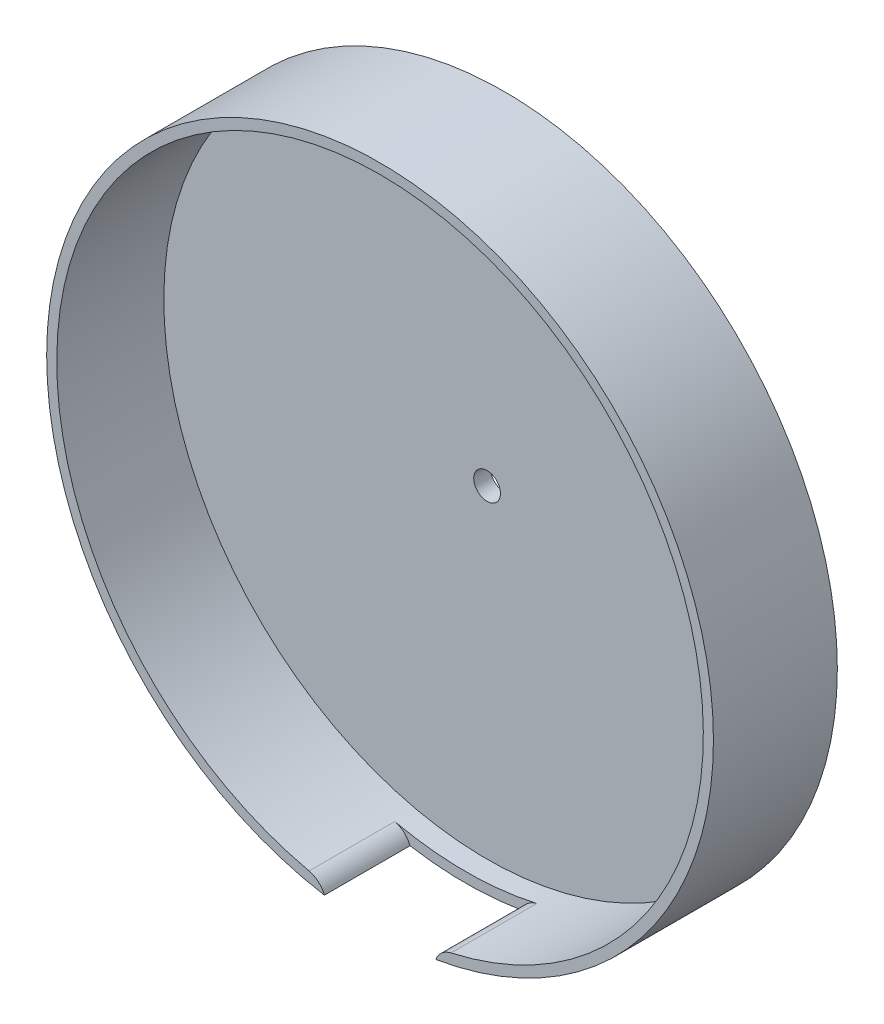
SolidWorks part; units mm, degrees
ref_plane "Front Plane" through (0, 0, 0) normal (0, 0, 1) x (1, 0, 0)
ref_plane "Top Plane" through (0, 0, 0) normal (0, 1, 0) x (1, 0, 0)
ref_plane "Right Plane" through (0, 0, 0) normal (1, 0, 0) x (0, 0, -1)
sketch "Sketch1" plane through (0, 0, 0) normal (0, 0, 1) x (1, 0, 0)
  circle A0 centre (0, 0) radius 38.1
  circle A1 centre (0, 0) radius 35.941
  dimension "D1" = 71.882
  dimension "D2" = 76.2
sketch "Sketch2" plane through (0, 0, 0) normal (0, 0, 1) x (1, 0, 0)
  circle A0 centre (0, 0) radius 38.354
  circle A1 centre (0, 0) radius 39.554
  circle A2 centre (0, 0) radius 38.1 construction
  dimension "D1" = 0.254
  dimension "D2" = 1.2
extrude "Boss-Extrude1" add sketch "Sketch2" along normal blind 12.7
extrude "Boss-Extrude2" add sketch "Sketch2<2>" against normal blind 2 contours A1 A0 | A0 region at (-38.4352, 0, 0)
sketch "Sketch2<2>" plane through (0, 0, 0) normal (0, 0, 1) x (1, 0, 0) same geometry as "Sketch2"
sketch "Sketch4" plane through (0, 0, -2) normal (0, 0, -1) x (-1, 0, 0)
  circle A0 centre (0, 0) radius 1.5875
  dimension "D1" = 3.175
extrude "Cut-Extrude1" cut sketch "Sketch4" against normal through all
sketch "Sketch5" plane through (0, 0, 0) normal (0, 1, 0) x (1, 0, 0)
  line L0 (39.554, 2) -> (-39.554, 2) construction
  line L1 (-6.604, 2) -> (6.604, 2)
  line L2 (-6.604, 2) -> (-6.604, -12.7)
  line L3 (-6.604, -12.7) -> (6.604, -12.7)
  line L5 (1.5875, 2) -> (-1.5875, 2) construction
  line L7 (0, 9.8279) -> (0, 2) construction
  line L8 (6.604, 2) -> (6.604, -12.7)
  line L9 (0, -12.7) -> (0, -21.8353) construction
  line L10 (-6.604, 0) -> (6.604, 0)
  line L11 (6.604, -2.54) -> (-6.9286, -2.54)
  dimension "D1" = 13.208
  dimension "D2" = 6.604
  dimension "D3" = 2.54
extrude "Cut-Extrude3" cut sketch "Sketch5" against normal up to surface (38.9988 mm away) contours L10 L2 L3 L8 region at (0, 0, 7.62) up to face at (39.554, 0, 12.7)
fillet "Fillet1" radius 2.54 2 edges at (-6.604, -37.7812, 7.62) (6.604, -37.7812, 7.62)
equation "\"D2@Sketch5\"=\"D1@Sketch5\"/2"
